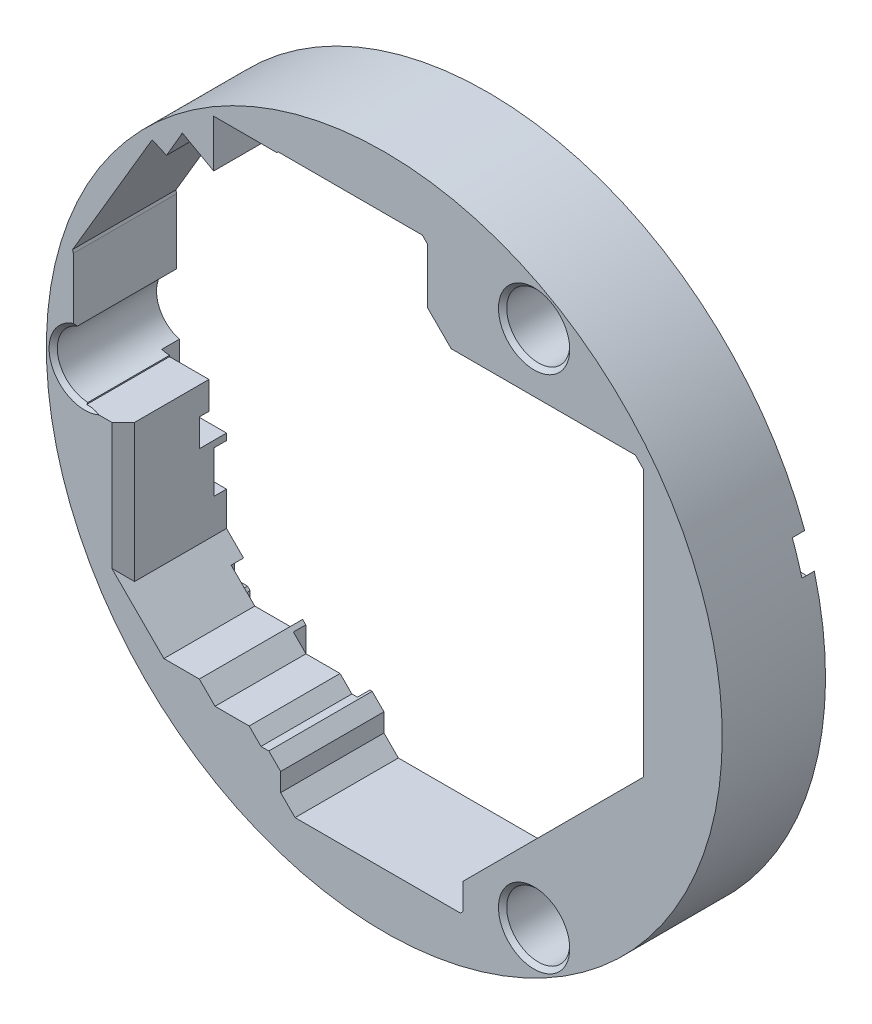
SolidWorks part; units mm, degrees
material "丙烯酸(中高冲击)"
ref_plane "前视基准面" through (0, 0, 0) normal (0, 0, 1) x (1, 0, 0)
ref_plane "上视基准面" through (0, 0, 0) normal (0, 1, 0) x (1, 0, 0)
ref_plane "右视基准面" through (0, 0, 0) normal (1, 0, 0) x (0, 0, -1)
sketch "草图1" plane through (0, 0, 0) normal (0, 0, 1) x (1, 0, 0)
  line L0 (72.39, 79.248) -> (74.422, 77.216)
  line L1 (71.882, 79.248) -> (72.39, 79.248)
  line L2 (71.501, 79.629) -> (71.882, 79.248)
  line L3 (70.866, 79.629) -> (71.501, 79.629)
  line L4 (69.596, 80.899) -> (69.596, 85.598)
  line L5 (69.596, 80.899) -> (70.866, 79.629)
  line L6 (74.422, 59.944) -> (74.422, 77.216)
  line L7 (74.422, 59.944) -> (78.359, 56.007)
  line L8 (78.359, 56.007) -> (81.788, 56.007)
  line L9 (81.788, 56.007) -> (83.312, 54.483)
  line L10 (83.312, 54.483) -> (86.614, 54.483)
  line L11 (86.614, 54.483) -> (87.757, 53.34)
  line L12 (87.757, 53.34) -> (88.519, 53.34)
  line L13 (88.519, 53.34) -> (89.662, 52.197)
  line L14 (89.662, 50.419) -> (89.662, 52.197)
  line L15 (89.662, 50.419) -> (91.059, 49.022)
  line L16 (91.059, 49.022) -> (107.061, 49.022)
  line L17 (107.061, 49.022) -> (107.315, 49.276)
  line L18 (107.315, 49.276) -> (107.315, 51.816)
  line L19 (107.315, 51.816) -> (122.809, 67.31)
  line L20 (122.809, 67.31) -> (122.809, 94.234)
  line L21 (121.158, 95.885) -> (122.809, 94.234)
  line L22 (106.172, 95.885) -> (121.158, 95.885)
  line L23 (103.886, 98.171) -> (106.172, 95.885)
  line L24 (103.886, 98.171) -> (103.886, 103.505)
  line L25 (103.378, 104.013) -> (103.886, 103.505)
  line L26 (89.408, 104.013) -> (103.378, 104.013)
  line L27 (89.281, 103.886) -> (89.408, 104.013)
  line L28 (89.281, 99.568) -> (89.281, 103.886)
  line L29 (88.265, 98.552) -> (89.281, 99.568)
  line L30 (84.6179, 98.4897) -> (88.265, 98.552)
  line L31 (82.677, 99.568) -> (84.6179, 98.4897)
  line L32 (80.137, 100.965) -> (82.677, 99.568)
  line L33 (80.01, 100.711) -> (80.137, 100.965)
  line L34 (77.2235, 98.9286) -> (78.6174, 98.3238)
  line L35 (69.5238, 85.8781) -> (77.2235, 98.9286)
  line L36 (69.5238, 85.8781) -> (69.596, 85.598)
  line L37 (78.6174, 98.3238) -> (80.01, 100.711)
sketch "草图2" plane through (0, 0, 0) normal (0, 0, 1) x (1, 0, 0)
  circle A0 centre (114.195, 101.5687) radius 3.05
  circle A3 centre (114.1951, 51.3391) radius 3.05
  circle A6 centre (70.6948, 76.454) radius 3.05
  circle A9 centre (99.695, 76.454) radius 32.7112
extrude "凸台-拉伸1" add sketch "草图2" along normal blind 10
extrude "切除-拉伸1" cut sketch "草图1" along normal up to surface (10 mm away) up to face at (117.2451, 51.3391, 10)
sketch "草图3" plane through (0, 0, 0) normal (0, 0, 1) x (1, 0, 0)
  line L1 (69.596, 80.899) -> (74.422, 80.899)
  line L2 (69.596, 80.899) -> (69.596, 77.216)
  line L3 (69.596, 77.216) -> (74.422, 77.216)
  line L4 (74.422, 80.899) -> (74.422, 77.216)
extrude "切除-拉伸2" cut sketch "草图3" along normal up to surface (10 mm away) up to face at (117.2451, 51.3391, 10)
sketch "草图4" plane through (0, 0, 0) normal (0, 0, 1) x (1, 0, 0)
  circle A0 centre (128.695, 76.454) radius 3.1
  circle A3 centre (85.195, 51.339) radius 3.1
  circle A6 centre (85.195, 101.569) radius 3.1
extrude "切除-拉伸3" cut sketch "草图4" along normal blind 1.2
sketch "草图5" plane through (0, 0, 0) normal (0, 0, 1) x (1, 0, 0)
  line L5 (88.265, 98.0709) -> (82.133, 98.0709)
  line L6 (88.265, 98.0709) -> (88.265, 101.9047)
  line L7 (88.265, 101.9047) -> (82.133, 101.9047)
  line L8 (82.133, 98.0709) -> (82.133, 101.9047)
  line L9 (88.2954, 51.3382) -> (82.095, 51.3382)
  line L10 (88.2954, 51.3382) -> (88.2954, 56.6846)
  line L11 (88.2954, 56.6846) -> (82.095, 56.6846)
  line L12 (82.095, 51.3382) -> (82.095, 56.6846)
  point P9 (82.0713, 56.7716)
  point P10 (88.3216, 56.6846)
  point P11 (88.2954, 51.3407)
  point P12 (82.095, 51.3382)
extrude "切除-拉伸7" cut sketch "草图5" along normal blind 1.2
sketch "草图6" plane through (0, 0, 0) normal (0, 0, 1) x (1, 0, 0)
  line L0 (70.739, 63.246) -> (70.739, 67.31)
  line L1 (70.739, 63.246) -> (74.803, 63.246)
  line L2 (74.803, 63.246) -> (74.803, 67.31)
  line L3 (70.739, 67.31) -> (74.803, 67.31)
  line L4 (75.692, 58.293) -> (81.788, 58.293)
  line L5 (81.788, 53.34) -> (81.788, 58.293)
  line L6 (78.105, 53.34) -> (81.788, 53.34)
  line L7 (77.851, 53.594) -> (78.105, 53.34)
  line L8 (77.851, 53.594) -> (77.851, 54.102)
  line L9 (77.724, 54.229) -> (77.851, 54.102)
  line L10 (76.962, 54.229) -> (77.724, 54.229)
  line L11 (76.708, 54.483) -> (76.962, 54.229)
  line L12 (76.708, 54.483) -> (76.708, 55.88)
  line L13 (76.454, 56.134) -> (76.708, 55.88)
  line L14 (75.438, 56.134) -> (76.454, 56.134)
  line L15 (75.184, 56.388) -> (75.438, 56.134)
  line L16 (75.184, 56.388) -> (75.184, 58.293)
  line L17 (75.184, 58.293) -> (76.327, 58.293)
  line L18 (94.742, 100.457) -> (103.886, 100.457)
  line L19 (94.742, 100.457) -> (94.742, 104.394)
  line L20 (103.886, 100.457) -> (103.886, 107.188)
  line L21 (94.742, 107.188) -> (103.886, 107.188)
  line L22 (94.742, 104.394) -> (94.742, 107.188)
  line L23 (131.318, 84.074) -> (131.318, 87.757)
  line L24 (123.952, 87.757) -> (131.318, 87.757)
  line L25 (123.952, 84.074) -> (131.318, 84.074)
  line L26 (123.952, 84.074) -> (123.952, 87.757)
extrude "切除-拉伸8" cut sketch "草图6" along normal blind 1.2 contours L17 L16 L15 L14 L13 L12 L11 L10 L9 L8 L7 L6 L5 L4 | L3 L0 L1 L2 | L26 L25 L23 L24 | L22 L19 L18 L20 L21 region at (72.771, 65.278, 0) region at (78.9298, 56.0637, 0) region at (99.314, 103.8225, 0) region at (127.635, 85.9155, 0)
sketch "草图7" plane through (0, 0, 0) normal (0, 0, 1) x (1, 0, 0)
  line L0 (94.107, 102.997) -> (94.107, 106.553)
  line L1 (89.281, 102.997) -> (94.107, 102.997)
  line L2 (89.281, 102.997) -> (89.281, 106.553)
  line L3 (89.281, 106.553) -> (94.107, 106.553)
  line L4 (74.549, 67.945) -> (75.057, 67.945)
  line L5 (75.057, 67.945) -> (75.057, 70.612)
  line L6 (69.723, 70.612) -> (75.057, 70.612)
  line L7 (69.723, 67.945) -> (69.723, 70.612)
  line L8 (69.723, 67.945) -> (74.549, 67.945)
extrude "切除-拉伸9" cut sketch "草图7" along normal blind 2.6
chamfer "倒角1" distance 0.4 angle 45 3 edges at (69.3002, 73.7415, 10) (117.2451, 51.3391, 10) (117.245, 101.5687, 10)
sketch "草图8" plane through (0, 0, 0) normal (0, 0, 1) x (1, 0, 0)
  line L0 (69.85, 68.072) -> (69.85, 72.39)
  line L1 (69.85, 68.072) -> (74.422, 68.072)
  line L2 (74.422, 68.072) -> (74.422, 71.882)
  line L3 (74.422, 71.882) -> (75.438, 72.898)
  line L4 (75.438, 72.898) -> (75.438, 78.74)
  line L5 (74.93, 79.248) -> (75.438, 78.74)
  line L6 (72.898, 79.248) -> (74.93, 79.248)
  line L7 (72.644, 78.994) -> (72.898, 79.248)
  line L8 (72.644, 73.787) -> (72.644, 78.994)
  line L9 (72.5308, 73.6738) -> (72.644, 73.787)
  line L10 (69.9869, 73.6738) -> (72.5308, 73.6738)
  line L11 (69.85, 73.5369) -> (69.9869, 73.6738)
  line L12 (69.85, 72.39) -> (69.85, 73.5369)
extrude "切除-拉伸10" cut sketch "草图8" along normal blind 1.7
sketch "草图9" plane through (0, 0, 0) normal (0, 0, 1) x (1, 0, 0)
  line L5 (70.6061, 73.2884) -> (75.9503, 73.2884)
  line L6 (70.6061, 73.2884) -> (70.6061, 77.8192)
  line L7 (70.6061, 77.8192) -> (75.9503, 77.8192)
  line L8 (75.9503, 73.2884) -> (75.9503, 77.8192)
extrude "切除-拉伸11" cut sketch "草图9" along normal up to surface (10 mm away) up to face at (117.6451, 51.3391, 10)
chamfer "倒角3" distance 2 angle 45 2 edges at (121.9835, 95.0595, 10) (122.809, 80.772, 10)
sketch "草图10" plane through (0, 0, 0) normal (0, 0, 1) x (1, 0, 0)
  line L1 (89.281, 103.886) -> (83.1811, 103.886)
  line L2 (89.281, 103.886) -> (89.281, 97.8668)
  line L3 (89.281, 97.8668) -> (83.1811, 97.8668)
  line L4 (83.1811, 103.886) -> (83.1811, 97.8668)
extrude "切除-拉伸12" cut sketch "草图10" along normal up to surface (10 mm away) up to face at (117.6451, 51.3391, 10)
chamfer "倒角5" distance 1.1 angle 45 1 edges at (74.422, 66.6162, 10)
